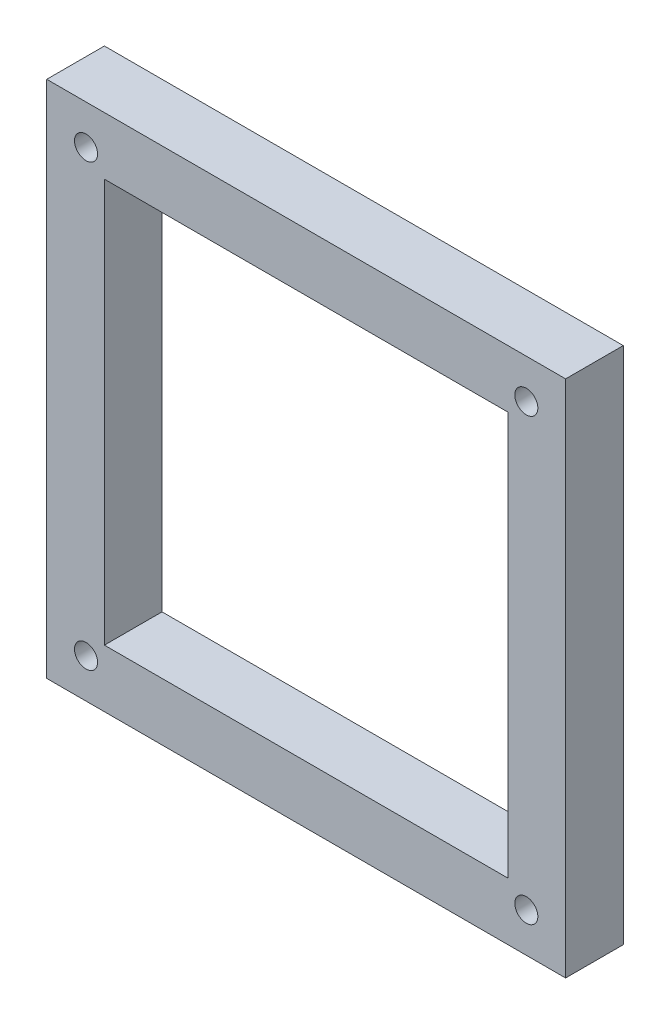
SolidWorks part; units mm, degrees
ref_plane "Front Plane" through (0, 0, 0) normal (0, 0, 1) x (1, 0, 0)
ref_plane "Top Plane" through (0, 0, 0) normal (0, 1, 0) x (1, 0, 0)
ref_plane "Right Plane" through (0, 0, 0) normal (1, 0, 0) x (0, 0, -1)
sketch "Sketch1" plane through (0, 0, 0) normal (0, 0, 1) x (1, 0, 0)
  line L0 (0, 45) -> (0, 0) construction
  line L1 (45, -45) -> (-45, -45)
  line L2 (45, -45) -> (45, 45)
  line L3 (45, 45) -> (-45, 45)
  line L4 (-45, -45) -> (-45, 45)
  line L5 (45, -45) -> (-45, 45) construction
  line L6 (45, 45) -> (-45, -45) construction
  line L7 (35, -35) -> (-35, -35)
  line L8 (35, -35) -> (35, 35)
  line L9 (35, 35) -> (-35, 35)
  line L10 (-35, -35) -> (-35, 35)
  line L11 (35, -35) -> (-35, 35) construction
  line L12 (35, 35) -> (-35, -35) construction
  line L13 (0, 0) -> (45, 0) construction
  circle A0 centre (-38.1838, 38.1838) radius 2
  circle A1 centre (38.1838, 38.1838) radius 2
  circle A2 centre (38.1838, -38.1838) radius 2
  circle A3 centre (-38.1838, -38.1838) radius 2
  point P0 (0, 0)
  point P6 (0, 0)
  dimension "D5" = 4
  dimension "D6" = 90
  dimension "D1" = 108
  dimension "D2" = 90
  dimension "D3" = 10
  dimension "D4" = 10
extrude "Boss-Extrude1" add sketch "Sketch1" along normal blind 10
sketch "Sketch3" plane through (0, 0, 0) normal (0, 0, -1) x (-1, 0, 0)
  circle A0 centre (-38.1838, 38.1838) radius 3.55
  circle A1 centre (38.1838, 38.1838) radius 3.55
  circle A2 centre (38.1838, -38.1838) radius 3.55
  circle A3 centre (-38.1838, -38.1838) radius 3.55
  dimension "D1" = 7.1
extrude "Cut-Extrude1" cut sketch "Sketch3" against normal blind 5
